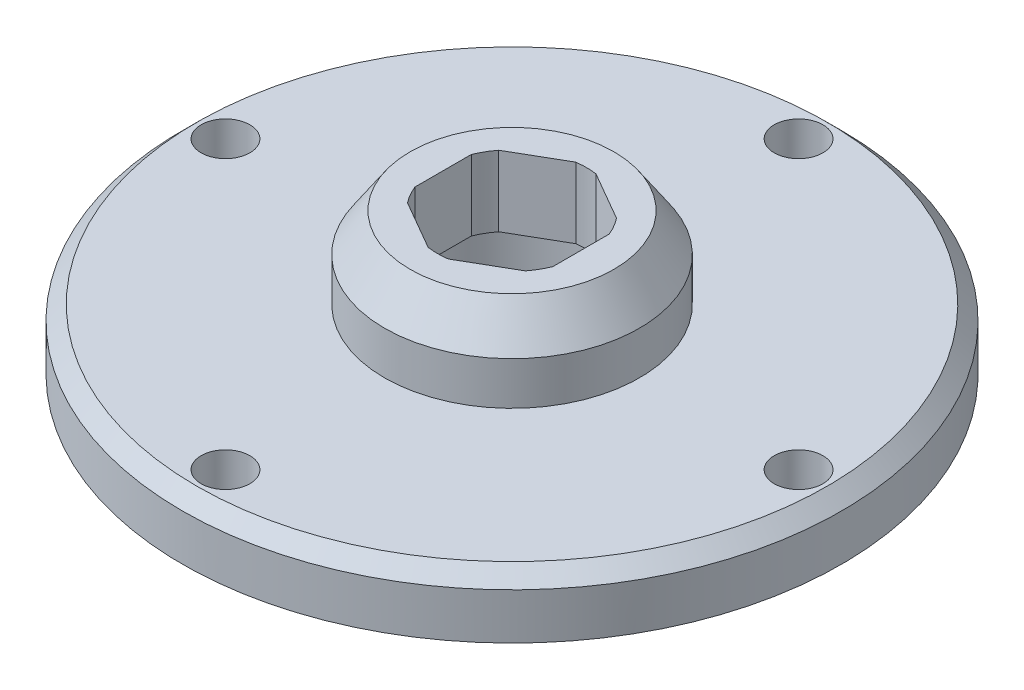
SolidWorks part; units mm, degrees
material "Nylon 6/10"
ref_plane "Front Plane" through (0, 0, 0) normal (0, 0, 1) x (1, 0, 0)
ref_plane "Top Plane" through (0, 0, 0) normal (0, 1, 0) x (1, 0, 0)
ref_plane "Right Plane" through (0, 0, 0) normal (1, 0, 0) x (0, 0, -1)
sketch "Sketch1" plane through (0, 0, 0) normal (0, 0, 1) x (1, 0, 0)
  line L0 (6.8, 0) -> (6.8, 4.953)
  line L1 (6.8, 4.953) -> (5.2, 4.953)
  line L2 (5.2, 4.953) -> (5.2, 9.8823)
  line L3 (5.2, 9.8823) -> (7.112, 9.8823)
  line L5 (8.9, 4.2198) -> (23, 4.2198)
  line L6 (23, 4.2198) -> (23, 0)
  line L7 (23, 0) -> (6.8, 0)
  line L8 (7.112, 9.8823) -> (8.9, 7.2198)
  line L9 (8.9, 7.2198) -> (8.9, 4.2198)
  line L10 (0, 0) -> (0, 16.4092) construction
  dimension "D1" = 6.8
  dimension "D2" = 23
  dimension "D3" = 4.953
  dimension "D4" = 8.9
  dimension "D5" = 5.6625
  dimension "D6" = 4.2198
  dimension "D7" = 3
  dimension "D8" = 7.112
  dimension "D9" = 5.2
revolve "Revolve1" add sketch "Sketch1" angle 360 about L10
sketch "Sketch2" plane through (0, 0, 0) normal (0, 1, 0) x (1, 0, 0)
  circle A0 centre (0, 0) radius 20 construction
  point P3 (-20, 0)
  dimension "D1" = 40
hole_wizard "M3 Clearance Hole1" positions "Sketch2" profile "Sketch3" hole size "M3" standard "ANSI Metric" end condition through all
sketch "Sketch3" plane through (-20, 0, 0) normal (1, 0, 0) x (0, 0, -1)
  line L0 (0, 0) -> (0, 9.8823)
  line L1 (0, 9.8823) -> (1.7, 9.8823)
  line L2 (1.7, 9.8823) -> (1.7, 0)
  line L5 (1.7, 0) -> (0, 0)
  line L11 (0, -6.35) -> (0, 107.95) construction
  dimension "Thru Hole Dia." = 3.4
  dimension "Thru Hole Depth" = 9.8823
pattern_circular "CirPattern1" count 4 over 360 about axis through (0, 0, 0) along (0, -1, 0) of "M3 Clearance Hole1"
sketch "Sketch4" plane through (0, 4.953, 0) normal (0, -1, 0) x (1, 0, 0)
  line L1 (4.8125, 2.7785) -> (0, 5.557)
  line L2 (0, 5.557) -> (-4.8125, 2.7785)
  line L3 (-4.8125, 2.7785) -> (-4.8125, -2.7785)
  line L4 (-4.8125, -2.7785) -> (0, -5.557)
  line L5 (0, -5.557) -> (4.8125, -2.7785)
  line L6 (4.8125, -2.7785) -> (4.8125, 2.7785)
  circle A0 centre (0, 0) radius 4.8125 construction
  circle A1 centre (0, 0) radius 5.2 construction
  circle A2 centre (0, 0) radius 5.2
  circle M9 centre (0, 0) radius 5.2
  dimension "D1" = 9.625
extrude "Boss-Extrude1" add sketch "Sketch4" against normal up to surface (4.9293 mm away) contours L2 M9 | L3 M9 | L4 M9 | L5 M9 | L6 M9 | L1 M9 region at (2.484, 4.953, 4.3024) region at (4.968, 4.953, 0) region at (-2.484, 4.953, 4.3024) region at (2.484, 4.953, -4.3024) region at (-4.968, 4.953, 0) region at (-2.484, 4.953, -4.3024) up to face at (0, 9.8823, -5.2)
chamfer "Chamfer1" distance 0.75 angle 45 1 edges at (0, 0, -6.8)
chamfer "Chamfer2" distance 1 angle 45 1 edges at (0, 4.2198, -23)
